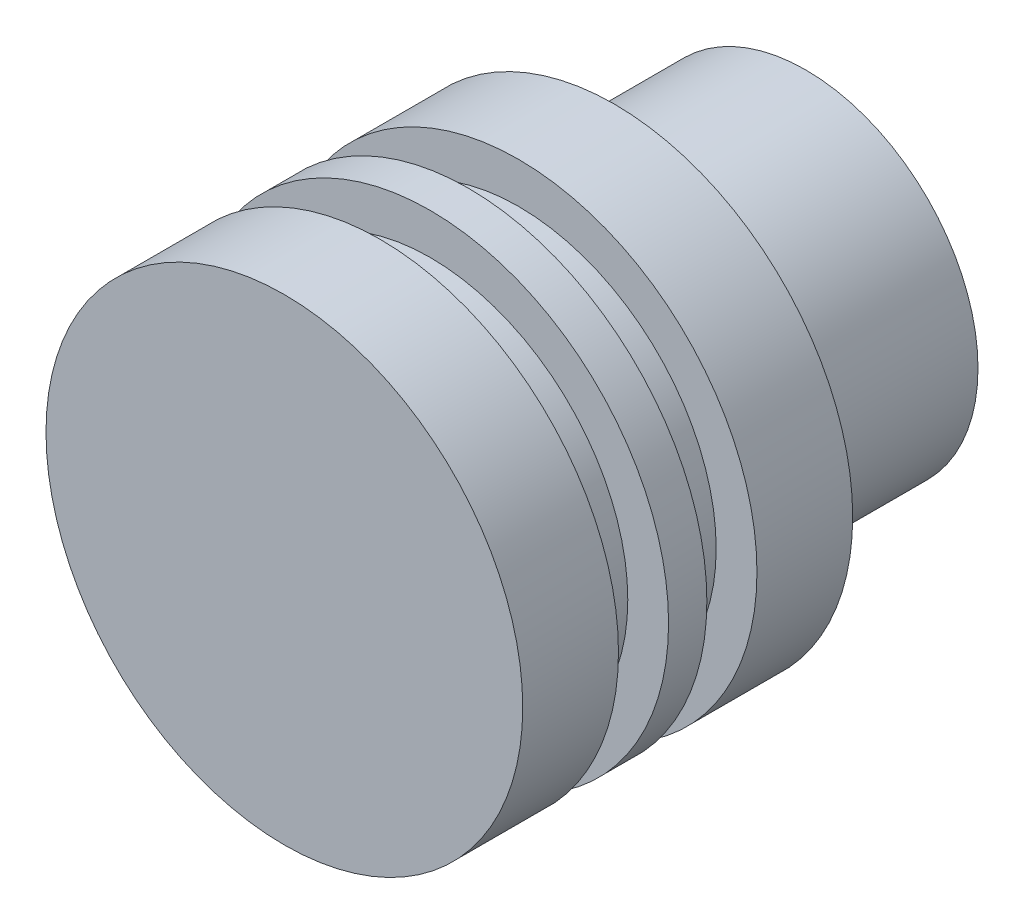
SolidWorks part; units mm, degrees
ref_plane "Front Plane" through (0, 0, 0) normal (0, 0, 1) x (1, 0, 0)
ref_plane "Top Plane" through (0, 0, 0) normal (0, 1, 0) x (1, 0, 0)
ref_plane "Right Plane" through (0, 0, 0) normal (1, 0, 0) x (0, 0, -1)
sketch "Sketch2" plane through (0, 0, 0) normal (1, 0, 0) x (0, 0, -1)
  line L0 (0, 0) -> (0, 12.45)
  line L1 (0, 12.45) -> (-5, 12.45)
  line L2 (-5, 12.45) -> (-5, 10.32)
  line L3 (-5, 10.32) -> (-7.6162, 10.32)
  line L4 (-7.6162, 10.32) -> (-7.6162, 12.45)
  line L5 (-7.6162, 12.45) -> (-9.6162, 12.45)
  line L6 (-9.6162, 12.45) -> (-9.6162, 10.32)
  line L7 (-9.6162, 10.32) -> (-12.2324, 10.32)
  line L8 (-12.2324, 10.32) -> (-12.2324, 12.45)
  line L9 (-12.2324, 12.45) -> (-17.2324, 12.45)
  line L10 (-17.2324, 12.45) -> (-17.2324, 0)
  line L11 (-17.2324, 0) -> (0, 0)
  dimension "D1" = 12.45
  dimension "D2" = 2.6162
  dimension "D3" = 2.6162
  dimension "D4" = 2
  dimension "D5" = 5
  dimension "D6" = 10.32
  dimension "D7" = 5
revolve "Revolve1" add sketch "Sketch2" angle 360 about L11
sketch "Sketch3" plane through (0, 0, 0) normal (0, 0, -1) x (-1, 0, 0)
  line L0 (0, -2.232) -> (0, 3.8523) construction
  circle A0 centre (0, 0) radius 8.9949
  circle A1 centre (0, 0) radius 5.9949
  dimension "D1" = 11.9898
  dimension "D2" = 3
extrude "Boss-Extrude4" add sketch "Sketch3" along normal blind 10 contours A0 | A1
sketch "Sketch4" [suppressed] plane through (0, 0, 17.2324) normal (0, 0, 1) x (1, 0, 0)
  circle A1 centre (0, 0) radius 12.45
  circle A2 centre (0, 0) radius 12.45
  dimension "D1" = 0
extrude "Boss-Extrude5" [suppressed] add sketch "Sketch4" along normal blind 15
sketch "Sketch5" [suppressed] plane through (0, 0, 0) normal (1, 0, 0) x (0, 0, -1)
  circle A0 centre (-24.9689, 0) radius 5
  dimension "D1" = 10
extrude "Cut-Extrude1" [suppressed] cut sketch "Sketch5" against normal through all both and the other way through all contours A0
